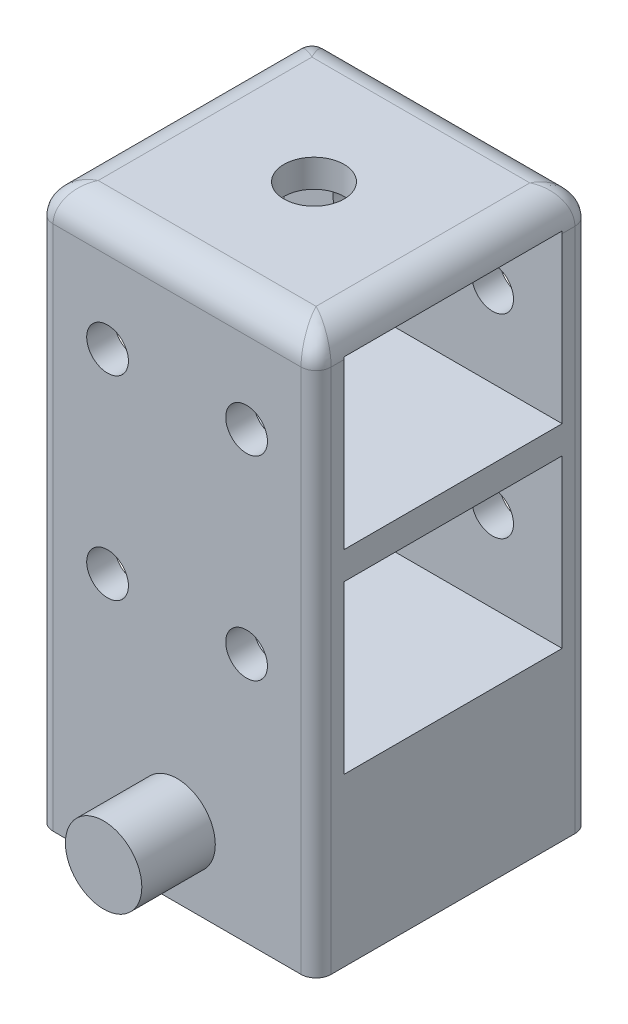
SolidWorks part; units mm, degrees
material "Aluminum 6061-T6"
ref_plane "Front Plane" through (0, 0, 0) normal (0, 0, 1) x (1, 0, 0)
ref_plane "Top Plane" through (0, 0, 0) normal (0, 1, 0) x (1, 0, 0)
ref_plane "Right Plane" through (0, 0, 0) normal (1, 0, 0) x (0, 0, -1)
sketch "Sketch1" plane through (0, 0, 0) normal (0, 1, 0) x (1, 0, 0)
  line L1 (-5, 4.925) -> (5, 4.925)
  line L2 (-5, 4.925) -> (-5, -4.925)
  line L3 (-5, -4.925) -> (5, -4.925)
  line L4 (5, 4.925) -> (5, -4.925)
  line L5 (-5, 4.925) -> (5, -4.925) construction
  line L6 (-5, -4.925) -> (5, 4.925) construction
  point P0 (0, 0)
  dimension "D1" = 9.85
  dimension "D2" = 10
extrude "Boss-Extrude1" add sketch "Sketch1" along normal blind 5
sketch "Sketch2" plane through (0, 0, 4.925) normal (0, 0, 1) x (1, 0, 0)
  line L0 (0, 5) -> (0, 2.5) construction
  line L1 (-5, 5) -> (5, 5) construction
  line L2 (0, 2.5) -> (-5, 2.5) construction
  line L3 (-5, 5) -> (-5, 0) construction
  circle A0 centre (0, 2.5) radius 1.375
  dimension "D1" = 2.75
extrude "Cut-Extrude1" cut sketch "Sketch2" against normal through all
sketch "Sketch3" plane through (5, 0, 0) normal (1, 0, 0) x (0, 0, -1)
  line L0 (-4.925, 5) -> (-4.925, 20)
  line L1 (-4.925, 20) -> (4.925, 20)
  line L2 (4.925, 20) -> (4.925, 5)
  line L3 (-4.925, 5) -> (4.925, 5)
  line L4 (-3.925, 6) -> (-3.925, 12)
  line L5 (-3.925, 19) -> (3.925, 19)
  line L6 (3.925, 19) -> (3.925, 13)
  line L8 (-3.925, 6) -> (3.925, 6)
  line L9 (-3.925, 13) -> (3.925, 13)
  line L10 (-3.925, 12) -> (3.925, 12)
  line L15 (-1.4894, 13) -> (-1.4894, 12) construction
  line L16 (-3.925, 13) -> (-3.925, 19)
  line L17 (-3.925, 6) -> (-3.925, 19) construction
  line L18 (3.925, 12) -> (3.925, 6)
  line L19 (3.925, 19) -> (3.925, 6) construction
  point P16 (-1.4894, 12.5)
  point P17 (-4.925, 12.5)
  dimension "D1" = 15
  dimension "D3" = 1
  dimension "D2" = 1
extrude "Boss-Extrude2" add sketch "Sketch3" against normal up to surface (10 mm away) up to face at (-5, 2.5, 0)
sketch "Sketch4" plane through (0, 0, 4.925) normal (0, 0, 1) x (1, 0, 0)
  line L0 (0, 19) -> (0, 16) construction
  line L1 (-5, 19) -> (5, 19) construction
  line L2 (-5, 19) -> (-5, 13) construction
  line L3 (0, 16) -> (-5, 16) construction
  line L5 (-5, 12.4999) -> (5, 12.4999) construction
  line L6 (-5, 20) -> (-5, 0) construction
  line L7 (5, 20) -> (5, 0) construction
  line L8 (-5, 13) -> (5, 13) construction
  circle A0 centre (-2.5, 16) radius 0.75
  circle A1 centre (2.5, 16) radius 0.75
  circle A2 centre (2.5, 8.9999) radius 0.75
  circle A3 centre (-2.5, 8.9999) radius 0.75
  dimension "D1" = 1.5
  dimension "D2" = 0.5001
extrude "Cut-Extrude2" cut sketch "Sketch4" against normal up to surface (9.85 mm away) up to face at (1.375, 2.5, -4.925)
sketch "Sketch5" plane through (0, 20, 0) normal (0, 1, 0) x (1, 0, 0)
  circle A0 centre (0, 0) radius 1.5
  dimension "D1" = 3
extrude "Cut-Extrude3" cut sketch "Sketch5" against normal up to surface (1 mm away) up to face at (0, 19, 0)
scale "Scale1" scale about centroid uniform scaling yes scale factor 1.85
sketch "Sketch6" plane through (0, 30.3095, 0) normal (0, 1, 0) x (1, 0, 0)
  circle A0 centre (0, 0) radius 2
  circle A1 centre (0, 0) radius 2.775
  circle A2 centre (0, 0) radius 2.775 construction
  dimension "D1" = 4
extrude "Boss-Extrude3" add sketch "Sketch6" against normal up to surface (1.85 mm away) up to face at (0, 28.4595, 2.775)
fillet "Fillet2" radius 2 6 edges at (0, 30.3095, -9.1113) (0, 30.3095, 9.1113) (9.25, 30.3095, 0) (-9.25, 28.4595, 0) (9.25, 28.4595, 0) (-9.25, 30.3095, 0)
fillet "Fillet3" radius 1 8 edges at (9.25, 10.8095, 9.1113) (-9.25, 10.8095, 9.1113) (-9.25, 10.8095, -9.1113) (9.25, 10.8095, -9.1113) (-8.6642, 29.7237, -8.5255) (8.6642, 29.7237, -8.5255) (-8.6642, 29.7237, 8.5255) (8.6642, 29.7237, 8.5255)
sketch "Sketch7" plane through (0, 0, 0) normal (0, 0, 1) x (1, 0, 0)
  circle A0 centre (0, -2.0655) radius 2.5438
  circle A1 centre (0, -2.0655) radius 2.5438 construction
extrude "Boss-Extrude4" add sketch "Sketch7" along normal mid plane 28
